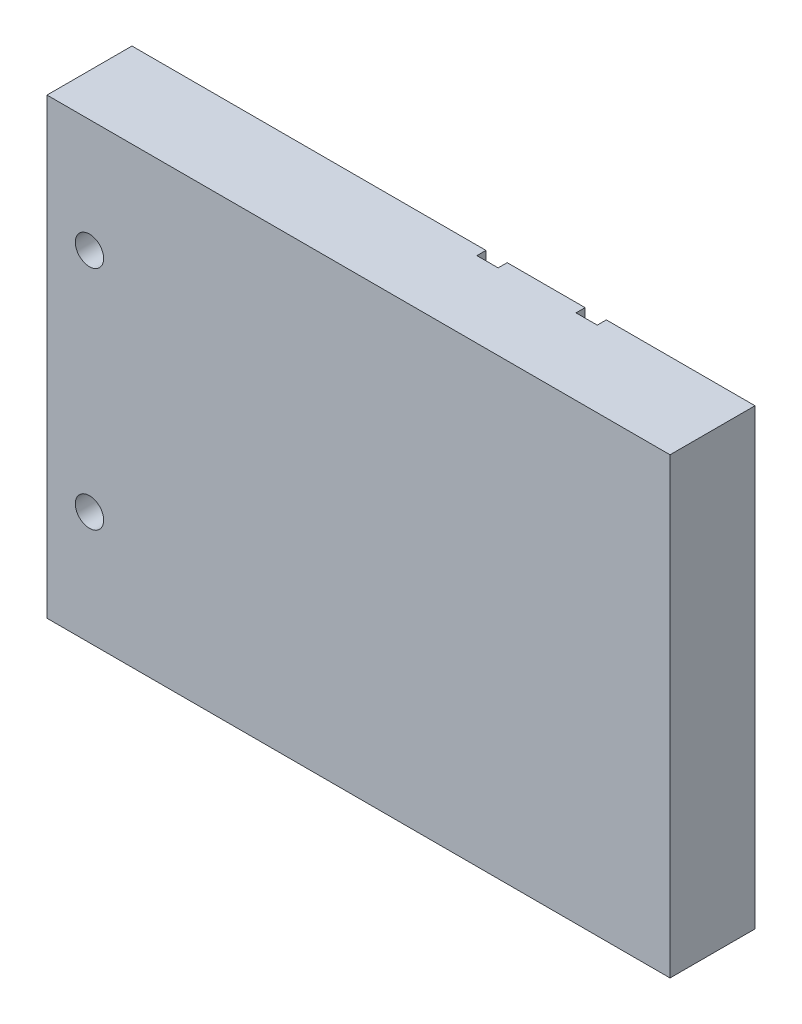
SolidWorks part; units mm, degrees
material "Pine"
ref_plane "Front Plane" through (0, 0, 0) normal (0, 0, 1) x (1, 0, 0)
ref_plane "Top Plane" through (0, 0, 0) normal (0, 1, 0) x (1, 0, 0)
ref_plane "Right Plane" through (0, 0, 0) normal (1, 0, 0) x (0, 0, -1)
sketch3d "3DSketch2"
  line L0 (69.85, 0, -9.525) -> (36.5125, 0, -9.525)
  line L1 (-69.85, 0, -9.525) -> (-69.85, 0, 9.525)
  line L2 (31.75, 0, -9.525) -> (14.2875, 0, -9.525)
  line L3 (69.85, 0, -9.525) -> (69.85, 0, 9.525)
  line L4 (-69.85, 0, 9.525) -> (69.85, 0, 9.525)
  line L5 (-69.85, 0, -9.525) -> (69.85, 0, 9.525) construction
  line L6 (69.85, 0, -9.525) -> (-69.85, 0, 9.525) construction
  line L7 (9.525, 0, -9.525) -> (9.525, 0, -7.493)
  line L8 (14.2875, 0, -9.525) -> (14.2875, 0, -7.493)
  line L9 (9.525, 0, -7.493) -> (14.2875, 0, -7.493)
  line L10 (9.525, 0, -9.525) -> (-69.85, 0, -9.525)
  line L11 (36.5125, 0, -9.525) -> (36.5125, 0, -7.493)
  line L12 (31.75, 0, -9.525) -> (31.75, 0, -7.493)
  line L13 (36.5125, 0, -7.493) -> (31.75, 0, -7.493)
  point P0 (0, 0, 0)
  point P6 (9.525, 0, -9.525)
  point P7 (36.5125, 0, -9.525)
  dimension "D1" = 139.7
  dimension "D2" = 19.05
  dimension "D3" = 33.3375
  dimension "D4" = 60.325
  dimension "D5" = 4.7625
  dimension "D6" = 2.032
extrude "Boss-Extrude3" add sketch "3DSketch2" along direction (0, 1, 0) on the side of the normal mid plane 101.6
hole_wizard "1/4 (0.25) Diameter Hole1" positions "Sketch7" profile "Sketch6" hole size "1/4" standard "Ansi Inch" end condition up to next
sketch "Sketch7" plane through (0, 0, -9.525) normal (0, 0, -1) x (-1, 0, 0)
  line L0 (69.85, -50.8) -> (69.85, 50.8) construction
  line L1 (-9.525, -50.8) -> (69.85, -50.8) construction
  line L2 (-9.525, 50.8) -> (69.85, 50.8) construction
  point P0 (60.325, -25.4)
  point P8 (60.325, 25.4)
  dimension "D1" = 9.525
  dimension "D2" = 25.4
  dimension "D3" = 25.4
sketch "Sketch6" plane through (-60.325, -25.4, -9.525) normal (1, 0, 0) x (0, 1, 0)
  line L0 (0, 0) -> (0, 19.05)
  line L1 (0, 19.05) -> (3.175, 19.05)
  line L2 (3.175, 19.05) -> (3.175, 0)
  line L5 (3.175, 0) -> (0, 0)
  line L11 (0, -6.35) -> (0, 107.95) construction
  dimension "Thru Hole Dia." = 6.35
  dimension "Thru Hole Depth" = 19.05
